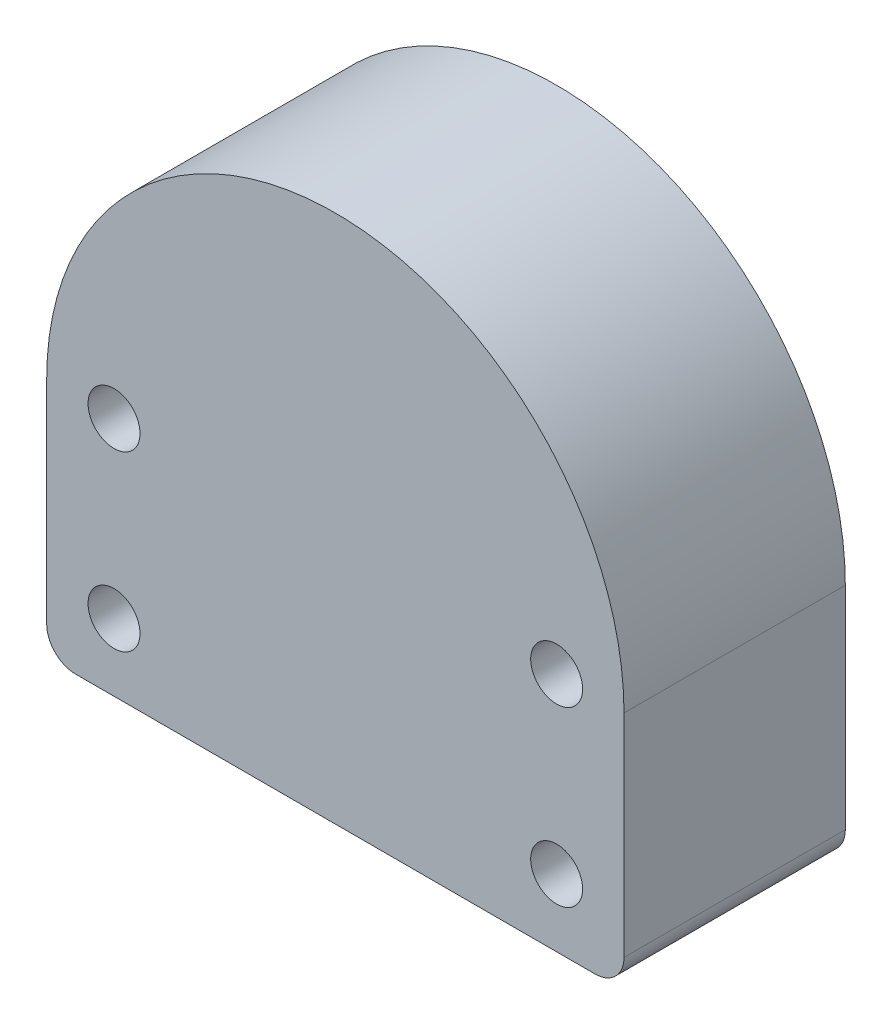
SolidWorks part; units mm, degrees
ref_plane "Front Plane" through (0, 0, 0) normal (0, 0, 1) x (1, 0, 0)
ref_plane "Top Plane" through (0, 0, 0) normal (0, 1, 0) x (1, 0, 0)
ref_plane "Right Plane" through (0, 0, 0) normal (1, 0, 0) x (0, 0, -1)
sketch "Sketch1" plane through (0, 0, 0) normal (0, 0, 1) x (1, 0, 0)
  line L1 (38.9055, 72) -> (38.9055, 47)
  line L4 (-21.0945, 72) -> (-21.0945, 47)
  line L6 (38.9055, 47) -> (-21.0945, 47)
  arc A2 (38.9055, 72) -> (-21.0945, 72) centre (8.9055, 72) ccw
  point P6 (38.9055, 46.6898)
  point P7 (38.9055, 47)
  point P8 (0, 0)
  point P9 (-22.678, 47)
  point P11 (0, 0)
  point P12 (-21.0945, 47)
  point P26 (0, 0)
  point P27 (0, 0)
  point P28 (36.7567, 81.1226)
  point P29 (37.5347, 84)
extrude "Boss-Extrude1" add sketch "Sketch1" along normal up to surface (23 mm away)
hole_wizard "M5 Clearance Hole1" positions "Sketch2" profile "Sketch3" hole size "M5" standard "ISO" end condition through all
sketch "Sketch2" plane through (0, 0, 23) normal (0, 0, -1) x (-1, 0, 0)
  point P0 (-31.9055, 72)
  point P2 (-31.9055, 54)
  point P4 (14.0945, 54)
  point P6 (14.0945, 72)
  point P11 (0, 0)
sketch "Sketch3" plane through (31.9055, 72, 23) normal (1, 0, 0) x (0, -1, 0)
  line L0 (0, 0) -> (0, 23)
  line L1 (0, 23) -> (2.7, 23)
  line L2 (2.7, 23) -> (2.7, 0)
  line L5 (2.7, 0) -> (0, 0)
  line L11 (0, -6.35) -> (0, 107.95) construction
  dimension "Thru Hole Dia." = 5.4
  dimension "Thru Hole Depth" = 23
fillet "Fillet1" radius 3 2 edges at (38.9055, 47, 11.5) (-21.0945, 47, 11.5)
